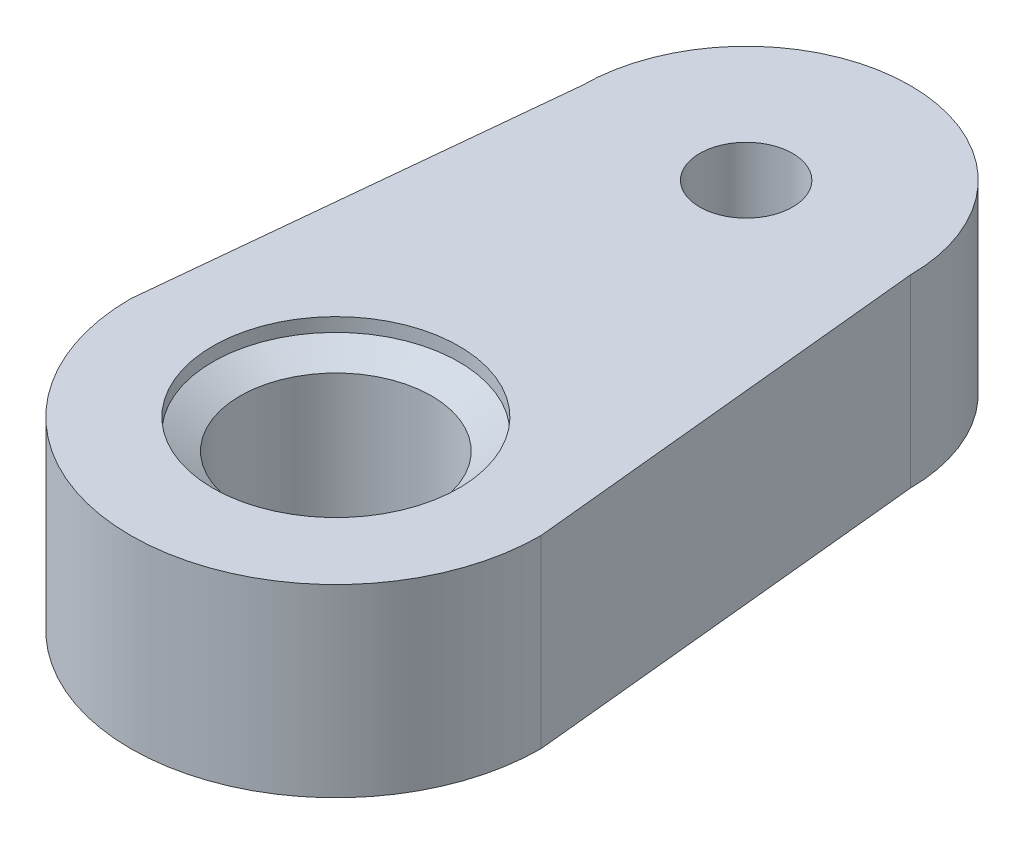
SolidWorks part; units mm, degrees
ref_plane "Front Plane" through (0, 0, 0) normal (0, 0, 1) x (1, 0, 0)
ref_plane "Top Plane" through (0, 0, 0) normal (0, 1, 0) x (1, 0, 0)
ref_plane "Right Plane" through (0, 0, 0) normal (1, 0, 0) x (0, 0, -1)
sketch "Sketch1" plane through (0, 0, 0) normal (0, 1, 0) x (1, 0, 0)
  line L0 (-1.2, 0.2213) -> (-1.5, -2.7787)
  line L1 (1.2, 0.2213) -> (1.5, -2.7787)
  arc A0 (-1.5, -2.7787) -> (1.5, -2.7787) centre (0, -2.7787) ccw
  arc A1 (1.2, 0.2213) -> (-1.2, 0.2213) centre (0, 0.2213) ccw
  circle A2 centre (0, -2.7787) radius 0.7
  circle A3 centre (0, 0.2213) radius 0.34
  dimension "D1" = 3
extrude "Boss-Extrude1" add sketch "Sketch1" along normal blind 1.35
sketch "Sketch2" plane through (0, 1.35, 0) normal (0, 1, 0) x (1, 0, 0)
  circle A0 centre (0, -2.7787) radius 0.9
extrude "Cut-Extrude3" cut sketch "Sketch2" against normal blind 0.35
chamfer "Chamfer1" distance 0.25 angle 60 1 edges at (0, 1, 3.6787) first distance on face at (0, 1, 3.6787)
